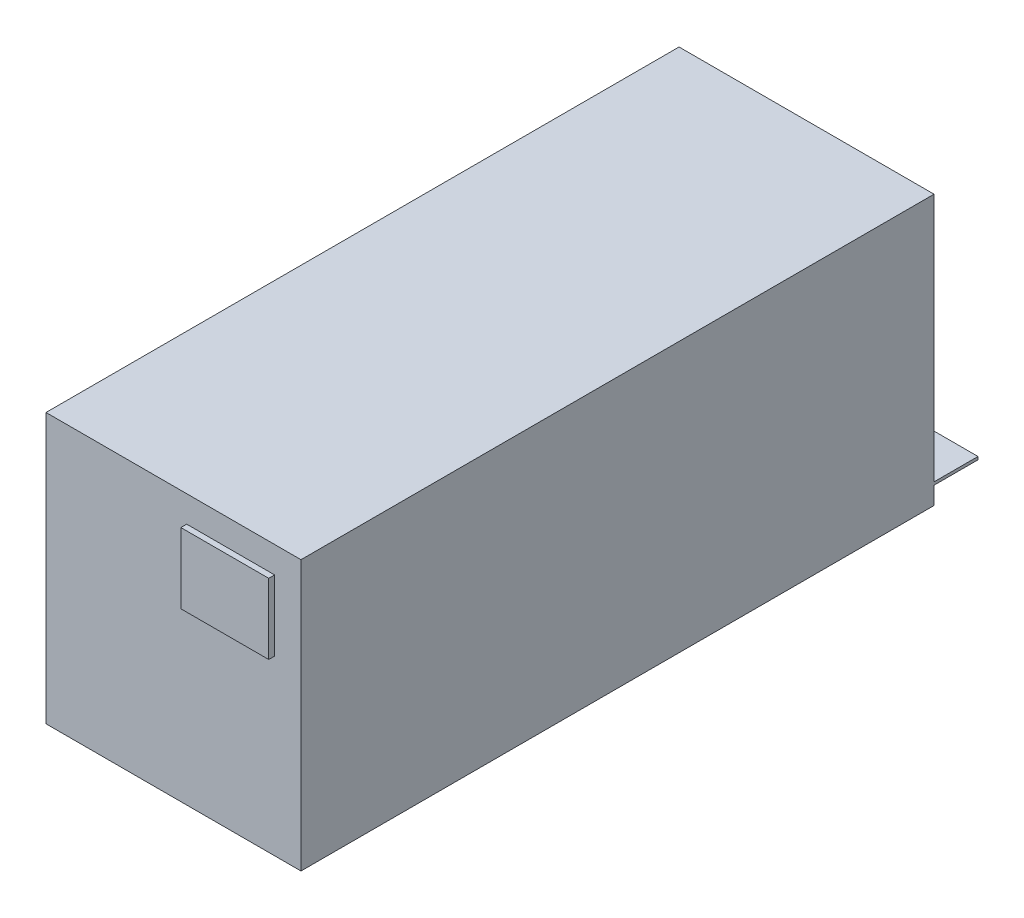
SolidWorks part; units mm, degrees
ref_plane "Płaszczyzna przednia" through (0, 0, 0) normal (0, 0, 1) x (1, 0, 0)
ref_plane "Płaszczyzna górna" through (0, 0, 0) normal (0, 1, 0) x (1, 0, 0)
ref_plane "Płaszczyzna prawa" through (0, 0, 0) normal (1, 0, 0) x (0, 0, -1)
sketch "Szkic1" plane through (0, 0, 0) normal (0, 0, 1) x (1, 0, 0)
  line L1 (-43.5, -46) -> (43.5, -46)
  line L2 (-43.5, -46) -> (-43.5, 46)
  line L3 (-43.5, 46) -> (43.5, 46)
  line L4 (43.5, -46) -> (43.5, 46)
  line L5 (-43.5, -46) -> (43.5, 46) construction
  line L6 (-43.5, 46) -> (43.5, -46) construction
  point P0 (0, 0)
  dimension "D1" = 87
  dimension "D2" = 92
extrude "Dodanie-wyciągnięcie1" add sketch "Szkic1" along normal blind 216
sketch "Szkic2" plane through (0, 0, 0) normal (0, 0, -1) x (-1, 0, 0)
  line L0 (-43.5, -46) -> (-43.5, 46) construction
  line L1 (-43.5, -40) -> (43.5, -40)
  line L2 (-43.5, -40) -> (-43.5, -39)
  line L3 (-43.5, -39) -> (43.5, -39)
  line L4 (43.5, -40) -> (43.5, -39)
  line L5 (43.5, 46) -> (43.5, -46) construction
  line L6 (43.5, -46) -> (-43.5, -46) construction
  dimension "D1" = 1
  dimension "D2" = 6
extrude "Dodanie-wyciągnięcie2" add sketch "Szkic2" along normal blind 15
sketch "Szkic3" plane through (0, 0, 216) normal (0, 0, 1) x (1, 0, 0)
  line L0 (43.5, -46) -> (43.5, 46) construction
  line L1 (4.5, 13) -> (34.5, 13)
  line L2 (4.5, 13) -> (4.5, 37)
  line L3 (4.5, 37) -> (34.5, 37)
  line L4 (34.5, 13) -> (34.5, 37)
  line L5 (43.5, 46) -> (-43.5, 46) construction
  dimension "D1" = 30
  dimension "D2" = 24
  dimension "D3" = 9
  dimension "D4" = 9
extrude "Dodanie-wyciągnięcie3" add sketch "Szkic3" along normal blind 2
sketch "Szkic4" plane through (0, -46, 0) normal (0, -1, 0) x (1, 0, 0)
  line L0 (-43.5, 216) -> (-43.5, 0) construction
  line L1 (-43.5, 216) -> (43.5, 216) construction
  circle A0 centre (-35.75, 208.75) radius 1.5
  circle A1 centre (35.75, 208.75) radius 1.5
  circle A2 centre (-35.75, 7.25) radius 1.5
  circle A3 centre (35.75, 7.25) radius 1.5
  point P8 (0, 0)
  point P9 (0, 0)
  point P10 (0, 0)
  point P11 (0, 0)
  dimension "D1" = 201.5
  dimension "D5" = 3
  dimension "D2" = 71.5
  dimension "D3" = 7.75
  dimension "D4" = 7.25
extrude "Wytnij-wyciągnięcie1" cut sketch "Szkic4" against normal blind 3
